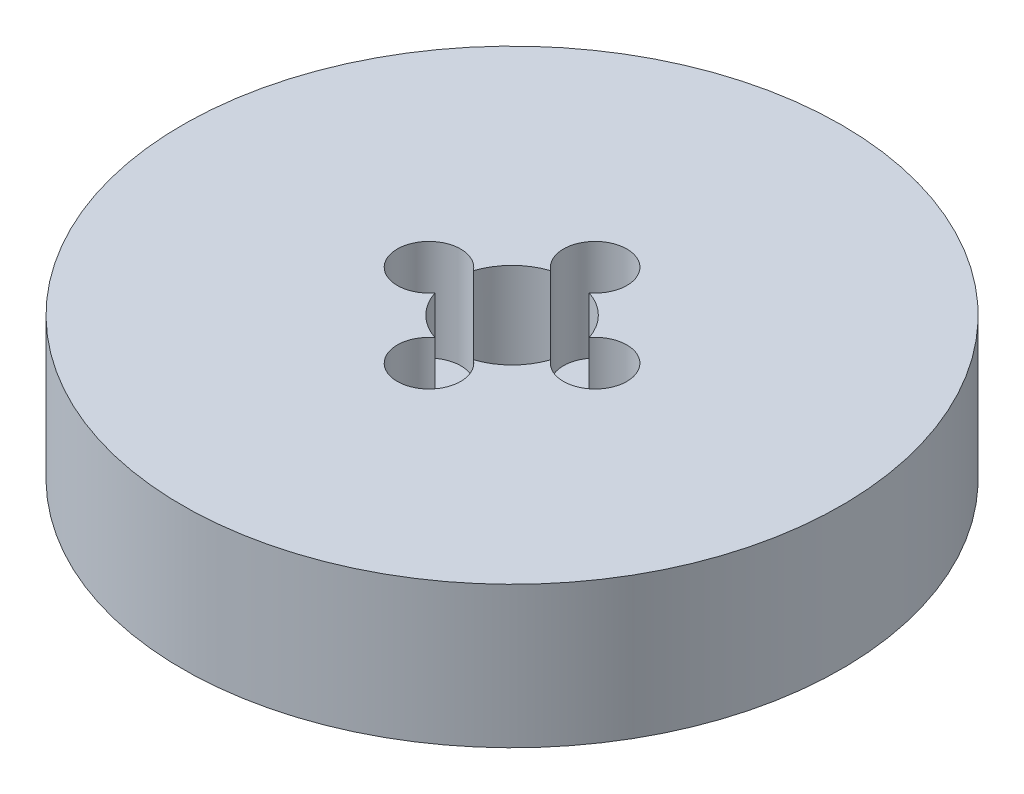
SolidWorks part; units mm, degrees
ref_plane "Front Plane" through (0, 0, 0) normal (0, 0, 1) x (1, 0, 0)
ref_plane "Top Plane" through (0, 0, 0) normal (0, 1, 0) x (1, 0, 0)
ref_plane "Right Plane" through (0, 0, 0) normal (1, 0, 0) x (0, 0, -1)
sketch "Sketch1" plane through (0, 0, 0) normal (0, 1, 0) x (1, 0, 0)
  circle A0 centre (0, 0) radius 67.5
  dimension "FLANGE_OD" = 135
extrude "Boss-Extrude1" add sketch "Sketch1" along normal blind 29
sketch "Sketch2" plane through (0, 0, 0) normal (0, 1, 0) x (1, 0, 0)
  circle A0 centre (0, 0) radius 12.5
  dimension "BORE_D" = 25
extrude "Cut-Extrude1" cut sketch "Sketch2" along normal through all
sketch "Sketch3" plane through (0, 29, 0) normal (0, 1, 0) x (1, 0, 0)
  circle A0 centre (0, 0) radius 17.0175 construction
  circle A1 centre (-17.0175, 0) radius 6.4889
  dimension "BOLT_D" = 12.9778
  dimension "BOLT_PCD" = 34.0351
extrude "Cut-Extrude2" cut sketch "Sketch3" against normal blind 20.707
pattern_circular "CirPattern1" count 4 over 360 about axis through (0, 0, 0) along (0, 1, 0) of "Cut-Extrude2"
